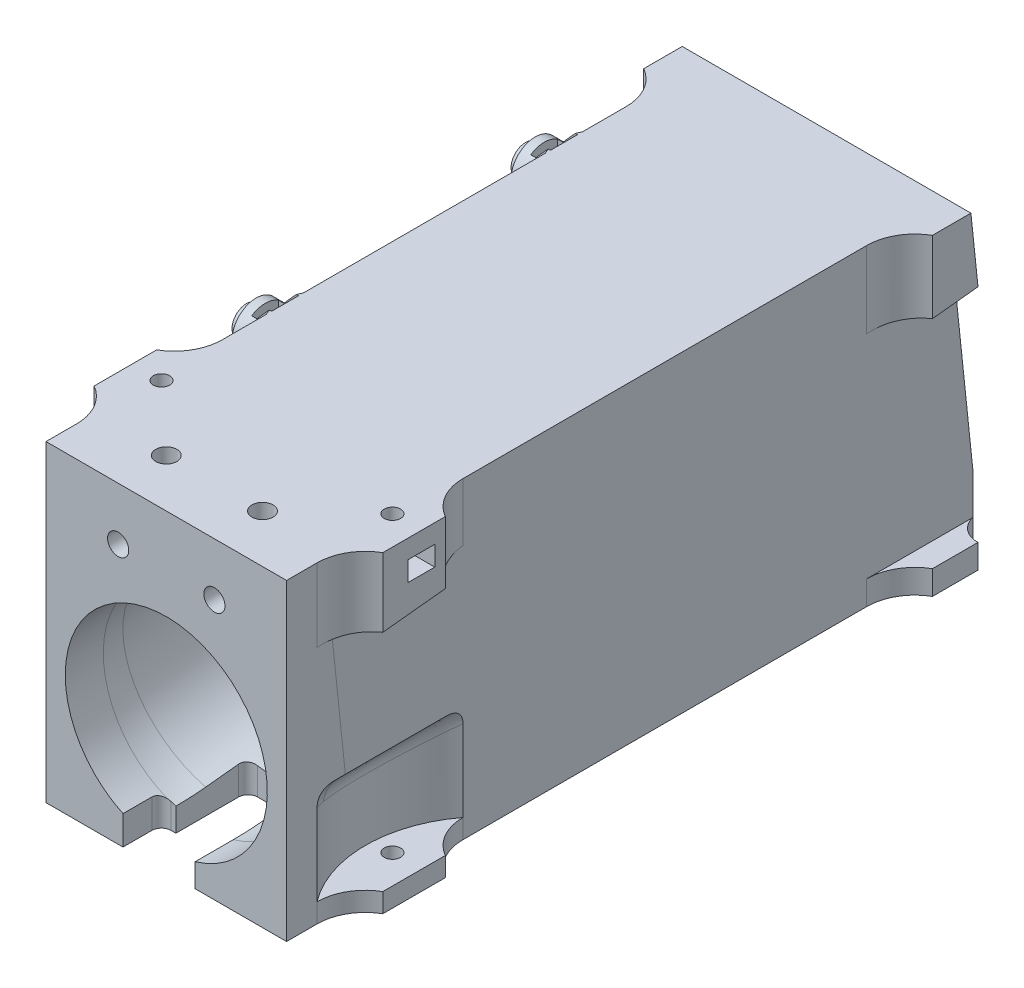
SolidWorks part; units mm, degrees
material "PVC 0.007 Plasticized"
ref_plane "Front Plane" through (0, 0, 0) normal (0, 0, 1) x (1, 0, 0)
ref_plane "Top Plane" through (0, 0, 0) normal (0, 1, 0) x (1, 0, 0)
ref_plane "Right Plane" through (0, 0, 0) normal (1, 0, 0) x (0, 0, -1)
sketch "Sketch1" plane through (0, 0, 0) normal (0, 0, 1) x (1, 0, 0)
  line L0 (25, 25) -> (30, 25)
  line L1 (-25, -25) -> (25, -25)
  line L2 (-25, -25) -> (-25, 25)
  line L3 (-25, 25) -> (25, 25) construction
  line L4 (25, -25) -> (25, 25)
  line L5 (-25, -25) -> (25, 25) construction
  line L6 (-25, 25) -> (25, -25) construction
  line L7 (-30, 25) -> (30, 25) construction
  line L8 (-30, 25) -> (-30, 40)
  line L9 (-30, 40) -> (30, 40)
  line L10 (30, 25) -> (30, 40)
  line L11 (-30, 25) -> (30, 40) construction
  line L12 (-30, 40) -> (30, 25) construction
  line L13 (-25, 25) -> (-30, 25)
  circle A0 centre (0, 0) radius 21
  point P0 (0, 0)
  point P8 (0, 32.5)
  dimension "D3" = 42
  dimension "D1" = 50
  dimension "D2" = 50
  dimension "D4" = 60
  dimension "D5" = 15
sketch "Sketch3" plane through (0, 0, 0) normal (1, 0, 0) x (0, 0, -1)
  line L0 (0, 0) -> (7.9037, 0)
  line L1 (12.0848, 0.2191) -> (140, 13.6636)
  line L2 (0, 25) -> (0, -25) construction
  arc A0 (7.9037, 0) -> (12.0848, 0.2191) centre (7.9037, 40) ccw
  point P8 (10, 0)
  dimension "D4" = 40
  dimension "D1" = 10
  dimension "D2" = 174
  dimension "D3" = 140
sweep "Sweep1" add profiles "Sketch1" path "Sketch3"
sketch "Sketch5" plane through (30, 0, 0) normal (1, 0, 0) x (0, 0, -1)
  line L0 (7.9037, 40) -> (137.2319, 40)
  line L1 (0, 40) -> (7.9037, 40) construction
  line L2 (7.9037, 40) -> (135.8189, 53.4444) construction
  line L3 (137.3868, 38.5266) -> (135.8189, 53.4444) construction
  line L4 (7.9037, 40) -> (135.8189, 53.4444)
  line L5 (137.2319, 40) -> (135.8189, 53.4444)
extrude "Cut-Extrude1" cut sketch "Sketch5" against normal through all
sketch "Sketch6" plane through (-30, 0, 0) normal (-1, 0, 0) x (0, 0, 1)
  line L0 (-28, 40) -> (-28, 27.0296)
  line L2 (0, 40) -> (0, 25) construction
  line L4 (-7.9037, 40) -> (-137.2319, 40) construction
  line L5 (-9.4716, 25.0822) -> (-137.3868, 38.5266) construction
  line L6 (-28, 27.0296) -> (-137.3868, 38.5266)
  line L9 (-28, 40) -> (-137.2319, 40)
  line L12 (-137.2319, 40) -> (-137.3868, 38.5266)
  line L13 (-15, 40) -> (-15, 25.6632)
  line L15 (0, 40) -> (-7.9037, 40) construction
  line L17 (0, 25) -> (-7.9037, 25) construction
  line L19 (-7.9037, 40) -> (-15, 40)
  line L20 (0, 40) -> (-7.9037, 40)
  line L21 (0, 40) -> (0, 25)
  line L22 (0, 25) -> (-7.9037, 25)
  line L23 (-9.4716, 25.0822) -> (-15, 25.6632)
  line L24 (-28, 27.0296) -> (-137.3868, 38.5266)
  line L25 (-28, 40) -> (-137.2319, 40)
  arc A2 (-9.4716, 25.0822) -> (-7.9037, 25) centre (-7.9037, 40) ccw construction
  arc A3 (-9.4716, 25.0822) -> (-7.9037, 25) centre (-7.9037, 40) ccw
  dimension "D1" = 28
  dimension "D2" = 15
extrude "Cut-Extrude2" cut sketch "Sketch6" against normal up to surface (5 mm away) contours L23 L13 L19 L20 L21 L22 A3 | L12 L6 L0 L9 up to face at (-25, 6.9413, -76.0424)
sketch "Sketch9" plane through (30, 0, 0) normal (1, 0, 0) x (0, 0, -1)
  line L2 (137.3868, 38.5266) -> (137.2319, 40) construction
  line L3 (137.2319, 40) -> (7.9037, 40) construction
  line L4 (9.4716, 25.0822) -> (137.3868, 38.5266) construction
  line L5 (7.9037, 40) -> (0, 40) construction
  line L7 (15, 25.6632) -> (28, 27.0296)
  line L8 (15, 40) -> (15, 25.6632)
  line L9 (28, 40) -> (15, 40)
  line L10 (28, 27.0296) -> (28, 40)
  line L18 (15, 40) -> (15, 25.6632)
  line L20 (28, 27.0296) -> (28, 40)
  line L21 (0, 40) -> (0, 25) construction
  line L22 (0, 25) -> (7.9037, 25) construction
  line L23 (137.3868, 38.5266) -> (137.2319, 40)
  line L24 (137.2319, 40) -> (28, 40)
  line L38 (9.4716, 25.0822) -> (15, 25.6632)
  line L39 (7.9037, 40) -> (0, 40)
  line L40 (0, 40) -> (0, 25)
  line L41 (0, 25) -> (7.9037, 25)
  line L42 (28, 27.0296) -> (137.3868, 38.5266)
  line L43 (15, 40) -> (7.9037, 40)
  arc A0 (7.9037, 25) -> (9.4716, 25.0822) centre (7.9037, 40) ccw construction
  arc A2 (7.9037, 25) -> (9.4716, 25.0822) centre (7.9037, 40) ccw
  dimension "D1" = 0
extrude "Cut-Extrude3" cut sketch "Sketch9" against normal up to surface (5 mm away) up to face at (25, 6.9413, -76.0424)
sketch "Sketch8" plane through (-25, 0, 0) normal (-1, 0, 0) x (0, 0, 1)
  line L0 (-137.2319, 40) -> (-138.7039, 25.9955)
  line L1 (-137.2319, 40) -> (-142.6132, -11.1995) construction
  line L2 (-138.7039, 25.9955) -> (-129.2319, 25)
  line L3 (-129.2319, 25) -> (-129.2319, 40)
  line L4 (-28, 40) -> (-137.2319, 40) construction
  line L5 (-129.2319, 40) -> (-137.2319, 40)
  dimension "D1" = 15
  dimension "D2" = 8
extrude "Boss-Extrude5" add sketch "Sketch8" along normal up to surface (5 mm away) up to face at (-30, 33.1732, -21.5)
sketch "Sketch10" plane through (25, 0, 0) normal (1, 0, 0) x (0, 0, -1)
  line L4 (138.7039, 25.9955) -> (137.2319, 40)
  line L5 (129.2319, 25) -> (138.7039, 25.9955)
  line L6 (129.2319, 40) -> (129.2319, 25)
  line L7 (137.2319, 40) -> (129.2319, 40)
  line L8 (138.7039, 25.9955) -> (137.2319, 40)
  line L9 (129.2319, 25) -> (138.7039, 25.9955)
  line L10 (129.2319, 40) -> (129.2319, 25)
  line L12 (137.2319, 40) -> (129.2319, 40)
  dimension "D1" = 0
extrude "Boss-Extrude6" add sketch "Sketch10" along normal up to surface (5 mm away) up to face at (30, 33.1732, -21.5)
fillet "Fillet2" radius 10 6 edges at (-25, 32.5, -129.2319) (25, 32.5, -129.2319) (-25, 33.5148, -28) (-25, 32.8316, -15) (25, 32.8316, -15) (25, 33.5148, -28)
sketch "Sketch11" plane through (0, 0, 0) normal (0, 0, 1) x (1, 0, 0)
  line L1 (-6, -7.1496) -> (6, -7.1496)
  line L2 (-6, -7.1496) -> (-6, -32.0234)
  line L3 (-6, -32.0234) -> (6, -32.0234)
  line L4 (6, -7.1496) -> (6, -32.0234)
  line L5 (-6, -7.1496) -> (6, -32.0234) construction
  line L6 (-6, -32.0234) -> (6, -7.1496) construction
  point P0 (0, -19.5865)
  dimension "D1" = 12
extrude "Cut-Extrude4" cut sketch "Sketch11" against normal blind 23
sketch "Sketch12" plane through (0, -25, 0) normal (0, -1, 0) x (1, 0, 0)
  line L18 (-6, -7.9037) -> (-25, -7.9037) construction
  line L25 (25, -7.9037) -> (6, -7.9037) construction
  line L29 (25, -14.698) -> (6, -14.698)
  line L30 (6, -14.698) -> (6, -23)
  line L31 (6, -23) -> (-6, -23)
  line L32 (-6, -23) -> (-6, -14.698)
  line L33 (-6, -14.698) -> (-25, -14.698)
  line L34 (-25, -14.698) -> (-25, -142.6132)
  line L35 (-25, -142.6132) -> (25, -142.6132)
  line L36 (25, -142.6132) -> (25, -14.698)
  line L38 (6, -14.698) -> (6, -23)
  line L39 (6, -23) -> (-6, -23)
  line L40 (-6, -23) -> (-6, -14.698)
  line L42 (-25, -14.698) -> (-25, -36.6603)
  line L43 (-25, -142.6132) -> (25, -142.6132)
  line L44 (25, -36.6603) -> (25, -14.698)
  line L45 (-25, -14.698) -> (-6, -14.698) construction
  line L47 (-6, -7.9037) -> (-25, -7.9037)
  line L49 (25, -7.9037) -> (6, -7.9037)
  line L51 (6, -14.698) -> (25, -14.698) construction
  line L53 (25, -36.6603) -> (-25, -36.6603)
  line L54 (-25, -14.698) -> (-6, -14.698)
  line L55 (6, -14.698) -> (25, -14.698)
  arc A0 (-25, -36.6603) -> (-30, -28) centre (-35, -36.6603) ccw construction
  arc A1 (30, -28) -> (25, -36.6603) centre (35, -36.6603) ccw construction
  arc A10 (-25, -36.6603) -> (-30, -28) centre (-35, -36.6603) ccw construction
  arc A11 (30, -28) -> (25, -36.6603) centre (35, -36.6603) ccw construction
  dimension "D1" = 0
extrude "Boss-Extrude7" add sketch "Sketch12" against normal up to surface (0.3561 mm away) contours L38 L39 L40 L54 L42 L53 L44 L55
sketch "Sketch13" plane through (0, -25, 0) normal (0, -1, 0) x (1, 0, 0)
  line L0 (-25, -14.698) -> (-6, -14.698) construction
  line L1 (-6, -14.698) -> (-6, -7.9037) construction
  line L2 (-6, -7.9037) -> (-25, -7.9037) construction
  line L3 (-25, -7.9037) -> (-25, -14.698) construction
  line L4 (25, -7.9037) -> (6, -7.9037) construction
  line L5 (6, -7.9037) -> (6, -14.698) construction
  line L6 (6, -14.698) -> (25, -14.698) construction
  line L7 (25, -14.698) -> (25, -7.9037) construction
  line L8 (-25, -14.698) -> (-6, -14.698)
  line L9 (-6, -14.698) -> (-6, -7.9037)
  line L10 (-6, -7.9037) -> (-25, -7.9037)
  line L11 (-25, -7.9037) -> (-25, -14.698)
  line L12 (25, -7.9037) -> (6, -7.9037)
  line L13 (6, -7.9037) -> (6, -14.698)
  line L14 (6, -14.698) -> (25, -14.698)
  line L15 (25, -14.698) -> (25, -7.9037)
extrude "Boss-Extrude8" add sketch "Sketch13" against normal up to surface up to face at (15.5, -24.8664, -11.3032)
sketch "Sketch14" plane through (0, -25, 0) normal (0, -1, 0) x (1, 0, 0)
  line L0 (-25, -36.6603) -> (-25, -9.4716) construction
  line L1 (-25, -9.4716) -> (-25, -7.9037) construction
  line L2 (-25, -7.9037) -> (-25, -6.3397) construction
  line L3 (-30, -15) -> (-30, -28) construction
  line L4 (25, -9.4716) -> (25, -36.6603) construction
  line L5 (30, -28) -> (30, -15) construction
  line L6 (25, -6.3397) -> (25, -7.9037) construction
  line L7 (25, -7.9037) -> (25, -9.4716) construction
  line L8 (-25, -36.6603) -> (-25, -9.4716)
  line L9 (-25, -9.4716) -> (-25, -7.9037)
  line L10 (-25, -7.9037) -> (-25, -6.3397)
  line L11 (-30, -15) -> (-30, -28)
  line L12 (25, -9.4716) -> (25, -36.6603)
  line L13 (30, -28) -> (30, -15)
  line L14 (25, -6.3397) -> (25, -7.9037)
  line L15 (25, -7.9037) -> (25, -9.4716)
  arc A0 (-30, -15) -> (-25, -6.3397) centre (-35, -6.3397) ccw construction
  arc A1 (-25, -36.6603) -> (-30, -28) centre (-35, -36.6603) ccw construction
  arc A2 (30, -28) -> (25, -36.6603) centre (35, -36.6603) ccw construction
  arc A3 (25, -6.3397) -> (30, -15) centre (35, -6.3397) ccw construction
  arc A4 (-30, -15) -> (-25, -6.3397) centre (-35, -6.3397) ccw
  arc A5 (-25, -36.6603) -> (-30, -28) centre (-35, -36.6603) ccw
  arc A6 (30, -28) -> (25, -36.6603) centre (35, -36.6603) ccw
  arc A7 (25, -6.3397) -> (30, -15) centre (35, -6.3397) ccw
extrude "Boss-Extrude9" add sketch "Sketch14" against normal blind 4
sketch "Sketch15" plane through (0, -25, 0) normal (0, -1, 0) x (1, 0, 0)
  line L4 (25, -36.6603) -> (-25, -36.6603)
  line L5 (-25, -36.6603) -> (-25, -142.6132)
  line L6 (-25, -142.6132) -> (25, -142.6132)
  line L7 (25, -142.6132) -> (25, -36.6603)
  line L8 (25, -36.6603) -> (-25, -36.6603)
  line L9 (-25, -36.6603) -> (-25, -142.6132)
  line L10 (-25, -142.6132) -> (25, -142.6132)
  line L11 (25, -142.6132) -> (25, -36.6603)
  dimension "D1" = 0
extrude "Boss-Extrude10" add sketch "Sketch15" against normal up to surface (13.8005 mm away)
sketch "Sketch16" plane through (0, -25, 0) normal (0, -1, 0) x (1, 0, 0)
  line L0 (-25, -138.7039) -> (-25, -120.5717) construction
  line L1 (-30, -129.2319) -> (-30, -138.7039) construction
  line L2 (-30, -138.7039) -> (-25, -138.7039) construction
  line L3 (25, -138.7039) -> (30, -138.7039) construction
  line L4 (30, -138.7039) -> (30, -129.2319) construction
  line L5 (25, -120.5717) -> (25, -138.7039) construction
  line L6 (-25, -138.7039) -> (-25, -120.5717)
  line L7 (-30, -129.2319) -> (-30, -138.7039)
  line L8 (-30, -138.7039) -> (-25, -138.7039)
  line L9 (25, -138.7039) -> (30, -138.7039)
  line L10 (30, -138.7039) -> (30, -129.2319)
  line L11 (25, -120.5717) -> (25, -138.7039)
  arc A0 (-30, -129.2319) -> (-25, -120.5717) centre (-35, -120.5717) ccw construction
  arc A1 (25, -120.5717) -> (30, -129.2319) centre (35, -120.5717) ccw construction
  arc A2 (-30, -129.2319) -> (-25, -120.5717) centre (-35, -120.5717) ccw
  arc A3 (25, -120.5717) -> (30, -129.2319) centre (35, -120.5717) ccw
extrude "Boss-Extrude11" add sketch "Sketch16" against normal blind 5
fillet "Fillet3" radius 5 4 edges at (25, -25, -140.6585) (-25, -25, -140.6585) (-25, -22.5, -138.7039) (25, -22.5, -138.7039)
sketch "Sketch17" plane through (0, 0, 0) normal (0, 0, 1) x (1, 0, 0)
  line L1 (-6, -25) -> (-9, -25)
  line L2 (-6, -25) -> (-6, -15.6664)
  line L3 (-6, -15.6664) -> (-9, -15.6664)
  line L4 (-9, -25) -> (-9, -15.6664)
  dimension "D1" = 3
extrude "Cut-Extrude5" cut sketch "Sketch17" against normal blind 8
fillet "Fillet4" radius 2 1 edges at (-9, -21.9868, -8)
fillet "Fillet5" radius 2 2 edges at (6, -21.9346, -23) (-6, -21.9346, -23)
sketch "Sketch18" plane through (0, 40, 0) normal (0, 1, 0) x (1, 0, 0)
  line L0 (25, 0) -> (-25, 0) construction
  line L1 (0, 0) -> (0, 18.1916) construction
  circle A0 centre (-10, 10) radius 2.2
  circle A1 centre (10, 10) radius 2.2
  dimension "D1" = 4.4
  dimension "D2" = 10
  dimension "D3" = 20
sketch "Sketch19" plane through (0, 40, 0) normal (0, 1, 0) x (1, 0, 0)
  circle A2 centre (-24, 23) radius 1.6 construction
  circle A3 centre (24, 23) radius 1.6 construction
  circle A4 centre (-24, 23) radius 1.6 construction
  circle A5 centre (24, 23) radius 1.6 construction
  circle A6 centre (24, 23) radius 1.7
  circle A7 centre (-24, 23) radius 1.7
  dimension "D1" = 3.4
  dimension "D2" = 3.4
extrude "Cut-Extrude7" cut sketch "Sketch19" against normal blind 10
ref_plane "Plane1" through (0, 32, 0) normal (0, 1, 0) x (1, 0, 0)
sketch "Sketch20" plane through (0, 32, 0) normal (0, 1, 0) x (1, 0, 0)
  line L0 (-31.2563, 25.8) -> (-36.0971, 20.2)
  line L1 (-20.7668, 23) -> (-22.3834, 25.8)
  line L2 (-22.3834, 25.8) -> (-31.2563, 25.8)
  line L5 (-36.0971, 20.2) -> (-22.3834, 20.2)
  line L6 (-22.3834, 20.2) -> (-20.7668, 23)
  line L8 (35.8269, 25.8) -> (22.3834, 25.8)
  line L9 (22.3834, 25.8) -> (20.7668, 23)
  line L10 (20.7668, 23) -> (22.3834, 20.2)
  line L11 (22.3834, 20.2) -> (35.8309, 20.2)
  line L13 (-25.676, 25.6971) -> (-27.2637, 22.9471)
  line L14 (-27.1738, 22.8971) -> (-25.586, 20.1471)
  line L15 (27.1738, 23.1029) -> (25.586, 25.8529)
  line L16 (25.676, 20.3029) -> (27.2637, 23.0529)
  line L17 (35.8269, 25.8) -> (35.8309, 20.2)
  circle A0 centre (24, 23) radius 1.7 construction
  circle A1 centre (24, 23) radius 1.7 construction
  circle A2 centre (-24, 23) radius 1.7 construction
  circle A3 centre (-24, 23) radius 1.7 construction
  circle A4 centre (-24, 23) radius 2.8 construction
  circle A5 centre (24, 23) radius 2.75 construction
  dimension "D1" = 5.6
  dimension "D2" = 5.6
extrude "Cut-Extrude8" cut sketch "Sketch20" along normal blind 4.1
sketch "Sketch21" plane through (0, -21, 0) normal (0, 1, 0) x (1, 0, 0)
  line L0 (25, 14.315) -> (25, 36.6603) construction
  line L1 (25, 36.6603) -> (25, 6.3397)
  arc A0 (25, 36.6603) -> (25, 6.3397) centre (44.8788, 21.5) ccw
  arc A1 (25, 36.6603) -> (30, 28) centre (35, 36.6603) ccw construction
  dimension "D1" = 25
extrude "Cut-Extrude9" cut sketch "Sketch21" along normal blind 10
sketch "Sketch22" plane through (0, -25, 0) normal (0, -1, 0) x (1, 0, 0)
  circle A0 centre (24, -23) radius 1.7 construction
  circle A1 centre (24, -23) radius 1.7
extrude "Cut-Extrude10" cut sketch "Sketch22" against normal blind 6
mirror "Mirror11" about plane through (0, 0, 0) normal (1, 0, 0) of "Cut-Extrude10", "Cut-Extrude9"
chamfer "Chamfer1" distance 10 angle 45 5 edges at (25, -11, -24.9621) (25, -11, -10.5838) (-25, -11, -7.1217) (-25, -11, -24.9621) (-25, -11, -10.5838)
fillet "Fillet8" radius 5 4 edges at (22.6787, -3.3213, -10.0041) (20.1078, -5.8922, -24.8763) (-22.6787, -3.3213, -10.0041) (-20.1078, -5.8922, -24.8763)
sketch "Sketch23" plane through (0, 0, 0) normal (0, 0, 1) x (1, 0, 0)
  circle A2 centre (-10, 29) radius 1.65 construction
  circle A3 centre (10, 29) radius 1.65 construction
  circle A4 centre (-10, 29) radius 1.65 construction
  circle A5 centre (10, 29) radius 1.65 construction
  circle A6 centre (-10, 29) radius 2.2
  circle A7 centre (10, 29) radius 2.2
  dimension "D1" = 4.4
  dimension "D2" = 4.4
extrude "Cut-Extrude11" cut sketch "Sketch23" against normal blind 8
extrude "Cut-Extrude12" cut sketch "Sketch18" against normal blind 8
sketch "Sketch24" plane through (0, 0, -142.6132) normal (0, 0, -1) x (-1, 0, 0)
  line L0 (0, 0) -> (0, -21.5989) construction
  line L1 (25, -11.1995) -> (-25, -11.1995) construction
  circle A0 centre (-15, -16.1995) radius 2.2
  circle A1 centre (15, -16.1995) radius 2.2
  dimension "D1" = 4.4
  dimension "D2" = 4.4
  dimension "D3" = 15
  dimension "D4" = 15
  dimension "D5" = 5
extrude "Cut-Extrude13" cut sketch "Sketch24" against normal blind 8
sketch "Sketch25" plane through (0, 14.7031, -139.8907) normal (0, 0.1045, -0.9945) x (-1, 0, 0)
  circle A0 centre (-15, 20) radius 2.2
  circle A1 centre (15, 20) radius 2.2
  dimension "D1" = 4.4
  dimension "D2" = 4.4
  dimension "D3" = 15
  dimension "D4" = 15
  dimension "D5" = 20
  dimension "D6" = 20
extrude "Cut-Extrude14" cut sketch "Sketch25" against normal blind 8
sketch "Sketch26" plane through (-25, 0, 0) normal (-1, 0, 0) x (0, 0, 1)
  line L0 (-36.6603, 40) -> (-120.5717, 40) construction
  line L1 (-36.6603, 27.9398) -> (-36.6603, 40) construction
  circle A0 centre (-107.6603, 33) radius 1.7
  circle A1 centre (-49.6603, 33) radius 1.7
  circle A2 centre (-107.6603, -16) radius 1.7
  circle A3 centre (-49.6603, -16) radius 1.7
  circle A4 centre (-107.6603, -16) radius 3
  circle A5 centre (-107.6603, 33) radius 3
  circle A6 centre (-49.6603, 33) radius 3
  circle A7 centre (-49.6603, -16) radius 3
  dimension "D3" = 3.4
  dimension "D4" = 3.4
  dimension "D5" = 3.4
  dimension "D6" = 3.4
  dimension "D9" = 6
  dimension "D10" = 6
  dimension "D11" = 6
  dimension "D12" = 6
  dimension "D1" = 49
  dimension "D2" = 58
  dimension "D7" = 7
  dimension "D8" = 13
extrude "Boss-Extrude12" add sketch "Sketch26" along normal blind 8
sketch "Sketch27" plane through (-25, 0, 0) normal (-1, 0, 0) x (0, 0, 1)
  circle A0 centre (-107.6603, 33) radius 5
  circle A1 centre (-49.6603, 33) radius 5
  circle A2 centre (-107.6603, -16) radius 5
  circle A3 centre (-49.6603, -16) radius 5
  circle A4 centre (-107.6603, -16) radius 1.7 construction
  circle A5 centre (-49.6603, -16) radius 1.7 construction
  circle A6 centre (-49.6603, 33) radius 1.7 construction
  circle A7 centre (-107.6603, 33) radius 1.7 construction
  circle A8 centre (-107.6603, -16) radius 1.7
  circle A9 centre (-49.6603, -16) radius 1.7
  circle A10 centre (-49.6603, 33) radius 1.7
  circle A11 centre (-107.6603, 33) radius 1.7
  dimension "D1" = 10
  dimension "D2" = 10
  dimension "D3" = 10
  dimension "D4" = 10
extrude "Boss-Extrude13" add sketch "Sketch27" along normal blind 6
sketch "Sketch28" plane through (-25, 0, 0) normal (-1, 0, 0) x (0, 0, 1)
  circle A0 centre (-49.6603, 33) radius 1.7 construction
  circle A1 centre (-49.6603, -16) radius 1.7 construction
  circle A2 centre (-107.6603, -16) radius 1.7 construction
  circle A3 centre (-107.6603, 33) radius 1.7 construction
  circle A4 centre (-49.6603, 33) radius 1.7
  circle A5 centre (-49.6603, -16) radius 1.7
  circle A6 centre (-107.6603, -16) radius 1.7
  circle A7 centre (-107.6603, 33) radius 1.7
extrude "Cut-Extrude15" cut sketch "Sketch28" against normal blind 4
sketch "Sketch29" plane through (-25, 0, 0) normal (-1, 0, 0) x (0, 0, 1)
  line L0 (-104.8603, 38.4313) -> (-110.4603, 38.2005)
  line L2 (-110.4603, 38.2005) -> (-110.4603, 31.3834)
  line L3 (-110.4603, 31.3834) -> (-107.6603, 29.7668)
  line L4 (-107.6603, 29.7668) -> (-104.8603, 31.3834)
  line L5 (-104.8603, 31.3834) -> (-104.8603, 38.4313)
  line L9 (-52.4603, 38.7994) -> (-52.4603, 31.3834)
  line L10 (-52.4603, 31.3834) -> (-49.6603, 29.7668)
  line L11 (-49.6603, 29.7668) -> (-46.8603, 31.3834)
  line L12 (-46.8603, 31.3834) -> (-46.8603, 38.6255)
  line L13 (-46.8603, 34.6166) -> (-49.6603, 36.2332)
  line L14 (-49.6603, 36.2332) -> (-52.4603, 34.6166)
  line L15 (-104.5397, 34.4315) -> (-107.3397, 36.0481)
  line L16 (-107.3397, 36.4182) -> (-110.1397, 34.8016)
  line L17 (-52.4603, 38.7994) -> (-46.8603, 38.6255)
  line L18 (-49.6603, -16) -> (-49.6603, 33) construction
  line L19 (-49.6603, 8.5) -> (-72.0646, 8.5) construction
  line L20 (-52.4603, -21.7994) -> (-46.8603, -21.6255)
  line L21 (-46.8603, -14.3834) -> (-46.8603, -21.6255)
  line L22 (-49.6603, -12.7668) -> (-46.8603, -14.3834)
  line L23 (-52.4603, -14.3834) -> (-49.6603, -12.7668)
  line L24 (-52.4603, -21.7994) -> (-52.4603, -14.3834)
  line L25 (-104.8603, -14.3834) -> (-104.8603, -21.4313)
  line L26 (-107.6603, -12.7668) -> (-104.8603, -14.3834)
  line L27 (-110.4603, -14.3834) -> (-107.6603, -12.7668)
  line L28 (-110.4603, -21.2005) -> (-110.4603, -14.3834)
  line L29 (-104.8603, -21.4313) -> (-110.4603, -21.2005)
  circle A0 centre (-107.6603, 33) radius 2.8 construction
  circle A1 centre (-49.6603, 33) radius 2.8 construction
  circle A2 centre (-49.6603, -16) radius 1.7 construction
  circle A3 centre (-49.6603, -16) radius 1.7 construction
  circle A4 centre (-49.6603, -16) radius 2.8 construction
  circle A5 centre (-107.6603, -16) radius 2.8 construction
  dimension "D1" = 5.6
  dimension "D2" = 5.6
extrude "Cut-Extrude16" cut sketch "Sketch29" along normal blind 4.1
chamfer "Chamfer2" distance 3 angle 45 4 edges at (-25, -11, -49.6603) (-25, -11, -107.6603) (-25, 28, -49.6603) (-25, 28, -107.6603)
